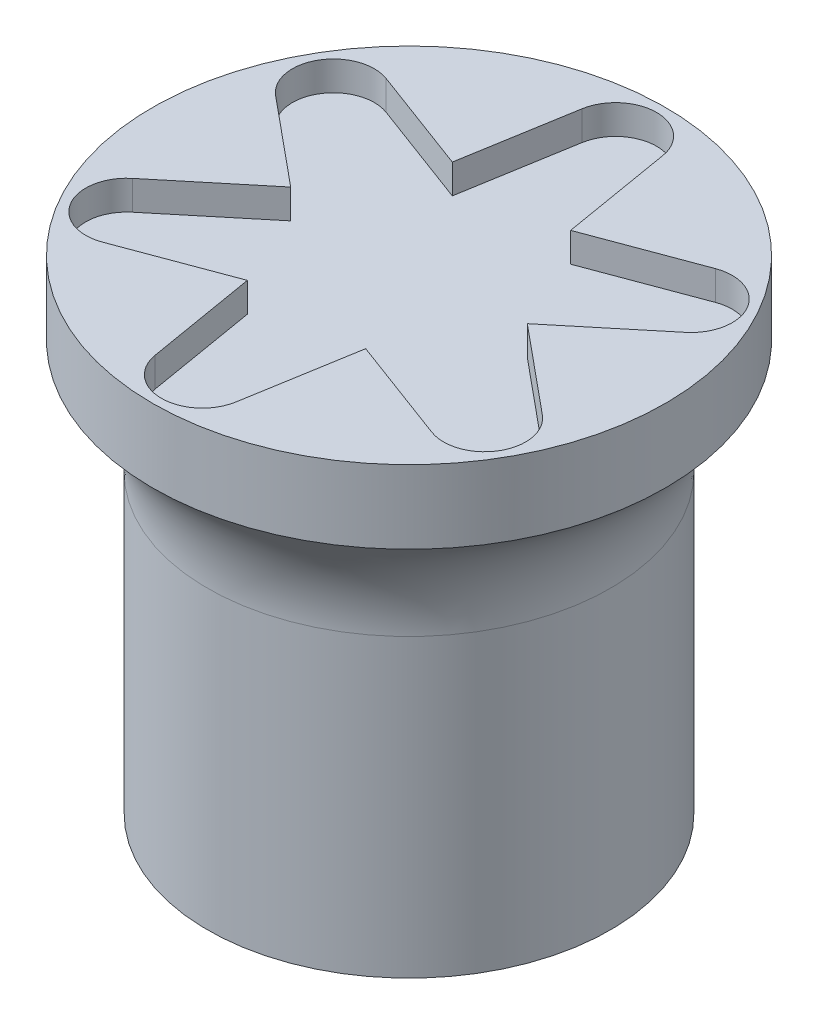
SolidWorks part; units mm, degrees
material "PLA"
ref_plane "Front Plane" through (0, 0, 0) normal (0, 0, 1) x (1, 0, 0)
ref_plane "Top Plane" through (0, 0, 0) normal (0, 1, 0) x (1, 0, 0)
ref_plane "Right Plane" through (0, 0, 0) normal (1, 0, 0) x (0, 0, -1)
sketch "Sketch1" plane through (0, 0, 0) normal (0, 1, 0) x (1, 0, 0)
  line L0 (4, 13.1553) -> (4, 7.7822)
  line L5 (-1.6, -3.9) -> (1.6, -3.9)
  line L6 (-1.6, 3.9) -> (1.6, 3.9)
  line L12 (-13.1553, -4) -> (-7.7822, -4)
  line L13 (-1.6, 0) -> (1.6, 0) construction
  line L14 (0, 0) -> (0, -3.9) construction
  arc A0 (-13.1553, -4) -> (4, 13.1553) centre (0, 0) ccw
  arc A2 (4, 7.7822) -> (-7.7822, -4) centre (0, 0) ccw
  arc A3 (-1.6, 3.9) -> (-1.6, -3.9) centre (-1.6, 0) ccw
  arc A4 (1.6, -3.9) -> (1.6, 3.9) centre (1.6, 0) ccw
  point P0 (0, 0)
  point P2 (-5.5, 0)
  point P4 (5.5, 0)
  dimension "D3" = 27.5
  dimension "D4" = 17.5
  dimension "D1" = 7.8
  dimension "D2" = 11
  dimension "D5" = 4
  dimension "D6" = 4
extrude "Boss-Extrude1" add sketch "Sketch1" against normal blind 3
sketch "Sketch2" plane through (0, 0, 0) normal (0, 1, 0) x (1, 0, 0)
  line L0 (-7.7822, -4) -> (-13.1553, -4) construction
  line L1 (-8.8917, -4) -> (-13.1553, -4)
  line L2 (4, 13.1553) -> (4, 7.7822) construction
  line L3 (4, 13.1553) -> (4, 8.8917)
  arc A0 (-8.8917, -4) -> (4, 8.8917) centre (0, 0) ccw
  arc A1 (-13.1553, -4) -> (4, 13.1553) centre (0, 0) ccw construction
  arc A2 (-13.1553, -4) -> (4, 13.1553) centre (0, 0) ccw
  dimension "D1" = 19.5
extrude "Boss-Extrude2" add sketch "Sketch2" along normal blind 25
sketch "Sketch3" plane through (0, 25, 0) normal (0, 1, 0) x (1, 0, 0)
  circle A0 centre (0, 0) radius 17.5
  dimension "D1" = 35
extrude "Boss-Extrude3" add sketch "Sketch3" along normal blind 5
sketch "Sketch4" plane through (0, 30, 0) normal (0, 1, 0) x (1, 0, 0)
  line L0 (-2.7611, 14.5654) -> (-4.0973, 6.6372)
  line L1 (2.7611, 14.5654) -> (4.0973, 6.6372)
  arc A0 (-4.0973, 6.6372) -> (4.0973, 6.6372) centre (0, 0) ccw
  arc A1 (2.7611, 14.5654) -> (-2.7611, 14.5654) centre (0, 14.1) ccw
  dimension "D1" = 15.6
  dimension "D2" = 5.6
  dimension "D3" = 14.1
  dimension "D4" = 8.04
  dimension "D5" = 8.04
extrude "Cut-Extrude1" cut sketch "Sketch4" against normal blind 2
pattern_circular "CirPattern1" count 6 over 360 about axis through (0, 28, 0) along (0, 1, 0) of "Cut-Extrude1"
fillet "Fillet1" radius 10 1 edges at (9.7227, 25, 9.7227)
